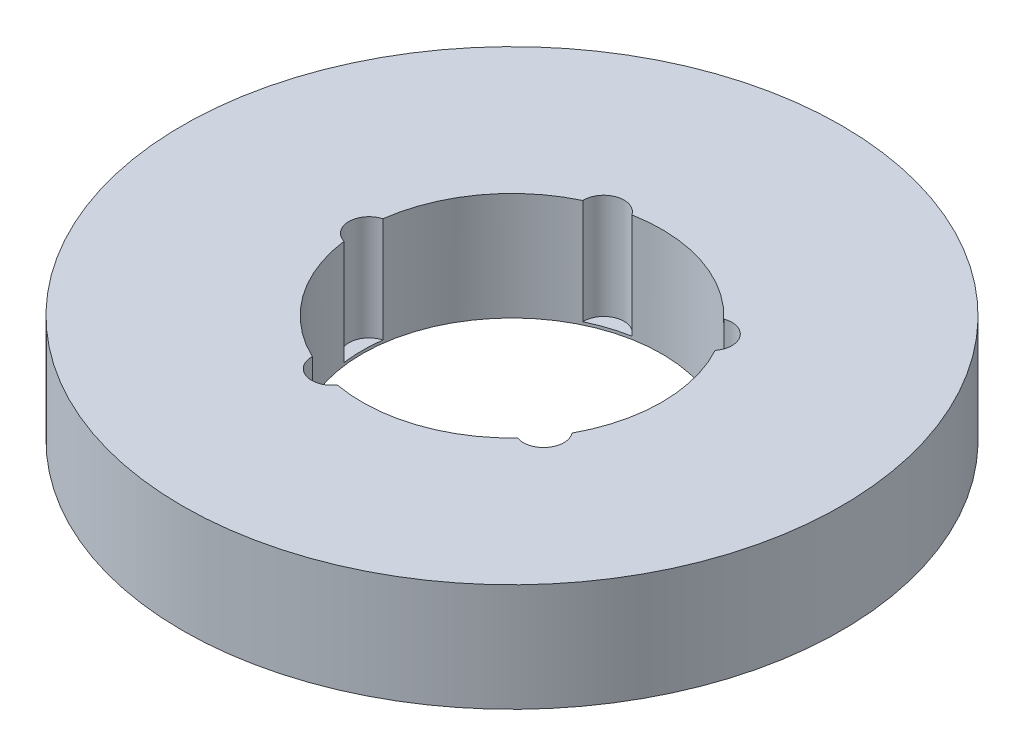
SolidWorks part; units mm, degrees
ref_plane "Front Plane" through (0, 0, 0) normal (0, 0, 1) x (1, 0, 0)
ref_plane "Top Plane" through (0, 0, 0) normal (0, 1, 0) x (1, 0, 0)
ref_plane "Right Plane" through (0, 0, 0) normal (1, 0, 0) x (0, 0, -1)
sketch "Sketch1" plane through (0, 0, 0) normal (0, 1, 0) x (1, 0, 0)
  circle A0 centre (0, 0) radius 82.5
  dimension "FLANGE_OD" = 165
extrude "Boss-Extrude1" add sketch "Sketch1" along normal blind 27
sketch "Sketch2" plane through (0, 0, 0) normal (0, 1, 0) x (1, 0, 0)
  circle A0 centre (0, 0) radius 37.5
  dimension "BORE_D" = 75
extrude "Cut-Extrude1" cut sketch "Sketch2" along normal through all
sketch "Sketch3" plane through (0, 27, 0) normal (0, 1, 0) x (1, 0, 0)
  circle A0 centre (0, 0) radius 35.7847 construction
  circle A1 centre (-35.7847, 0) radius 5.0694
  dimension "BOLT_D" = 10.1389
  dimension "BOLT_PCD" = 71.5693
extrude "Cut-Extrude2" cut sketch "Sketch3" against normal blind 26.2858
pattern_circular "CirPattern1" count 5 over 360 about axis through (0, 0, 0) along (0, 1, 0) of "Cut-Extrude2"
